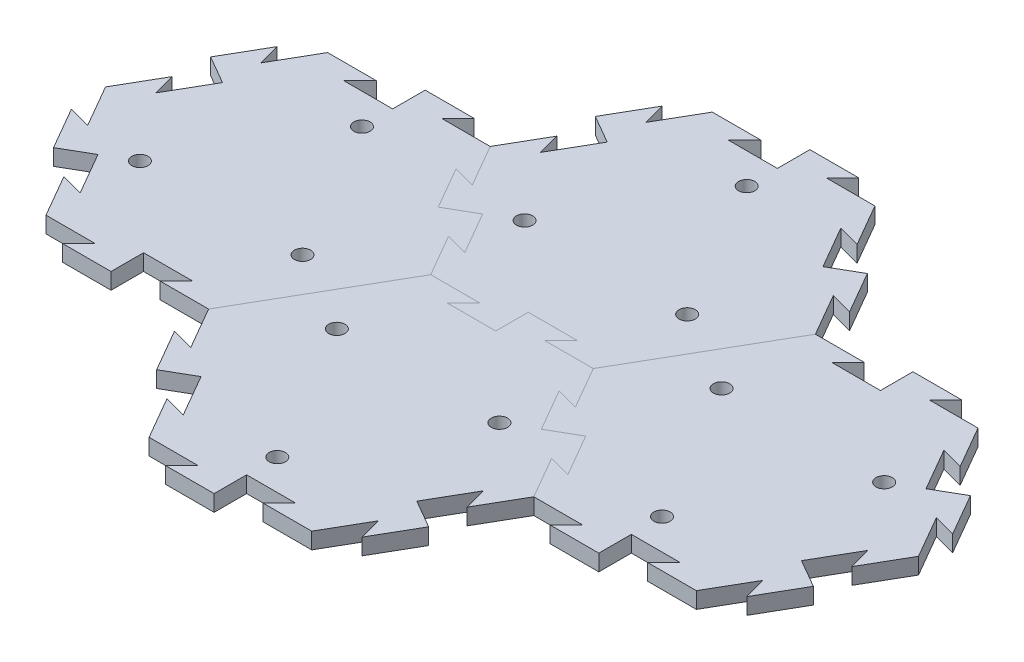
SolidWorks part; units mm, degrees
material "Cedar"
ref_plane "Front Plane" through (0, 0, 0) normal (0, 0, 1) x (1, 0, 0)
ref_plane "Top Plane" through (0, 0, 0) normal (0, 1, 0) x (1, 0, 0)
ref_plane "Right Plane" through (0, 0, 0) normal (1, 0, 0) x (0, 0, -1)
sketch "Sketch1" plane through (0, 0, 0) normal (0, 1, 0) x (1, 0, 0)
  line L0 (0, 0) -> (63.5, 0) construction
  line L1 (63.5, 0) -> (31.75, 54.9926)
  line L2 (31.75, 54.9926) -> (-31.75, 54.9926)
  line L3 (-31.75, 54.9926) -> (-63.5, 0)
  line L4 (-63.5, 0) -> (-31.75, -54.9926)
  line L5 (-31.75, -54.9926) -> (31.75, -54.9926)
  line L6 (31.75, -54.9926) -> (63.5, 0)
  circle A0 centre (0, 0) radius 54.9926 construction
  dimension "D1" = 63.5
extrude "Boss-Extrude1" add sketch "Sketch1" against normal blind 6.35
sketch "Sketch2" plane through (0, 0, 0) normal (0, 1, 0) x (1, 0, 0)
  point P1 (0, 0)
ref_axis "Axis1" through (0, 0, 0) along (0, 1, 0)
sketch "Sketch9" plane through (0, 0, 0) normal (0, 1, 0) x (1, 0, 0)
  line L1 (31.75, -18.3309) -> (0, 36.6617) construction
  line L2 (0, 36.6617) -> (-31.75, -18.3309) construction
  line L3 (-31.75, -18.3309) -> (31.75, -18.3309) construction
  circle A0 centre (0, 0) radius 18.3309 construction
  circle A1 centre (-31.75, -18.3309) radius 3.175
  dimension "D2" = 6.35
  dimension "D1" = 63.5
extrude "Cut-Extrude3" cut sketch "Sketch9" against normal through all
pattern_circular "CirPattern6" count 3 over 360 about axis through (0, 0, 0) along (0, 1, 0) of "Cut-Extrude3"
mirror "Mirror3" about plane through (31.75, -6.35, 54.9926) normal (0.866, 0, 0.5) of bodies 121 125
sketch "Sketch10" plane through (0, 0, 0) normal (0, 1, 0) x (1, 0, 0)
  line L0 (31.75, 54.9926) -> (41.275, 38.4948) construction
  line L1 (41.275, 38.4948) -> (32.6007, 40.8191)
  line L2 (32.6007, 40.8191) -> (42.1257, 24.3213)
  line L3 (42.1257, 24.3213) -> (47.625, 27.4963)
  line L4 (41.275, 38.4948) -> (47.625, 27.4963)
  line L5 (63.5, 0) -> (31.75, 54.9926) construction
  dimension "D1" = 45
  dimension "D2" = 6.35
extrude "Cut-Extrude4" cut sketch "Sketch10" against normal through all
sketch "Sketch11" plane through (0, 0, 0) normal (0, 1, 0) x (1, 0, 0)
  line L0 (47.625, 27.4963) -> (63.5, 0) construction
  line L1 (47.625, 27.4963) -> (53.1243, 30.6713)
  line L2 (53.1243, 30.6713) -> (62.6493, 14.1735)
  line L3 (62.6493, 14.1735) -> (53.975, 16.4978)
  line L4 (53.975, 16.4978) -> (47.625, 27.4963)
  line L5 (53.975, 16.4978) -> (63.5, 0) construction
  line L6 (53.975, 16.4978) -> (63.5, 0) construction
  line L7 (63.5, 0) -> (47.625, 27.4963) construction
  line L8 (31.75, -54.9926) -> (63.5, 0) construction
  dimension "D1" = 45
  dimension "D2" = 6.35
extrude "Boss-Extrude4" add sketch "Sketch11" against normal blind 6.35
pattern_circular "CirPattern7" count 6 over 360 about axis through (0, 0, 0) along (0, 1, 0) skipping 5 of "Cut-Extrude4", "Boss-Extrude4"
sketch "Sketch12" plane through (0, 0, 0) normal (0, 1, 0) x (1, 0, 0)
  line L0 (127, 0) -> (63.5, -109.9852) construction
  point P4 (95.25, -54.9926)
ref_axis "Axis2" through (95.25, 0, 54.9926) along (0, 1, 0)
sketch "Sketch13" plane through (0, 0, 0) normal (0, 1, 0) x (1, 0, 0)
  line L0 (127, 0) -> (136.525, -16.4978) construction
  line L1 (136.525, -16.4978) -> (127.8507, -14.1735)
  line L2 (127.8507, -14.1735) -> (137.3757, -30.6713)
  line L3 (137.3757, -30.6713) -> (142.875, -27.4963)
  line L4 (136.525, -16.4978) -> (142.875, -27.4963)
  line L5 (127, 0) -> (158.75, -54.9926) construction
  dimension "D1" = 45
  dimension "D2" = 6.35
extrude "Cut-Extrude5" cut sketch "Sketch13" against normal through all
sketch "Sketch14" plane through (0, 0, 0) normal (0, 1, 0) x (1, 0, 0)
  line L0 (142.875, -27.4963) -> (158.75, -54.9926) construction
  line L1 (142.875, -27.4963) -> (148.3743, -24.3213)
  line L2 (148.3743, -24.3213) -> (157.8993, -40.8191)
  line L3 (157.8993, -40.8191) -> (149.225, -38.4948)
  line L4 (149.225, -38.4948) -> (142.875, -27.4963)
  line L5 (149.225, -38.4948) -> (158.75, -54.9926) construction
  line L6 (149.225, -38.4948) -> (158.75, -54.9926) construction
  dimension "D1" = 45
  dimension "D2" = 6.35
extrude "Boss-Extrude5" add sketch "Sketch14" against normal blind 6.35
pattern_circular "CirPattern8" count 6 over 360 about axis through (95.25, 0, 54.9926) along (0, 1, 0) skipping 2 of "Cut-Extrude5", "Boss-Extrude5"
pattern_linear "LPattern1" count 2 spacing 109.9852 along (0.866, 0, -0.5) of bodies 125 129
